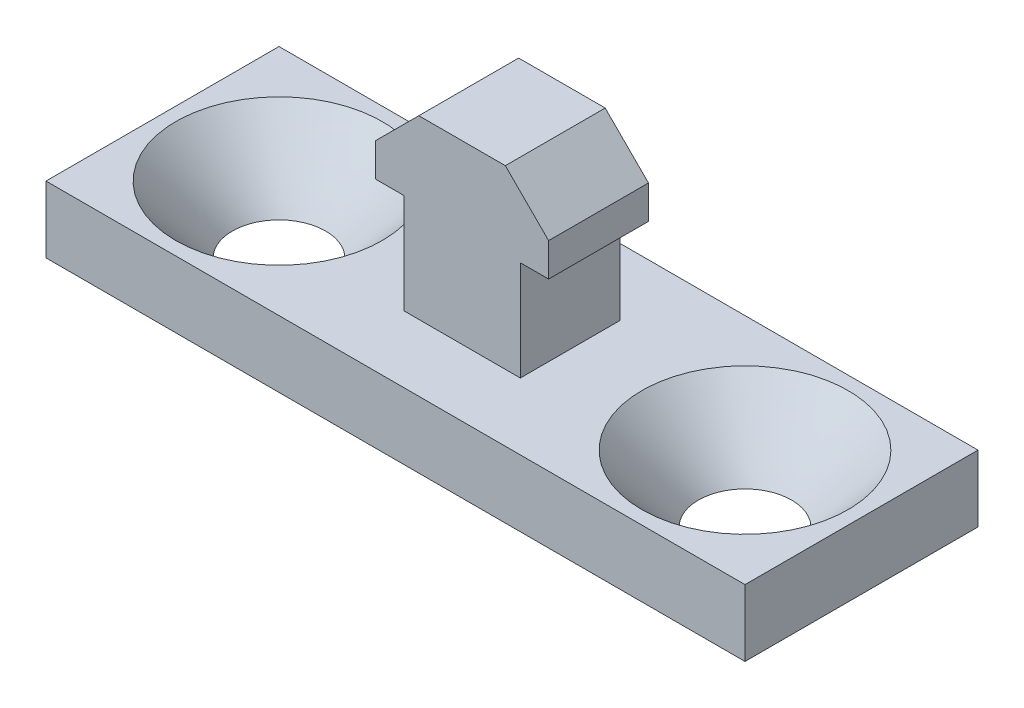
SolidWorks part; units mm, degrees
ref_plane "Front Plane" through (0, 0, 0) normal (0, 0, 1) x (1, 0, 0)
ref_plane "Top Plane" through (0, 0, 0) normal (0, 1, 0) x (1, 0, 0)
ref_plane "Right Plane" through (0, 0, 0) normal (1, 0, 0) x (0, 0, -1)
sketch "Sketch1" plane through (0, 0, 0) normal (0, 1, 0) x (1, 0, 0)
  line L1 (-10.5, -3.5) -> (10.5, -3.5)
  line L2 (-10.5, -3.5) -> (-10.5, 3.5)
  line L3 (-10.5, 3.5) -> (10.5, 3.5)
  line L4 (10.5, -3.5) -> (10.5, 3.5)
  line L5 (-10.5, -3.5) -> (10.5, 3.5) construction
  line L6 (-10.5, 3.5) -> (10.5, -3.5) construction
  point P0 (0, 0)
  dimension "D1" = 21
  dimension "D2" = 7
extrude "Boss-Extrude1" add sketch "Sketch1" along normal blind 2
sketch "Sketch2" plane through (0, 2, 0) normal (0, 1, 0) x (1, 0, 0)
  line L0 (-7, 0) -> (7, 0) construction
  circle A0 centre (-7, 0) radius 3.1
  circle A1 centre (7, 0) radius 3.1
  point P4 (0, 0)
  dimension "D2" = 6.2
  dimension "D1" = 14
sketch "Sketch3" plane through (0, 0, 0) normal (0, -1, 0) x (1, 0, 0)
  circle A0 centre (-7, 0) radius 1.4
  circle A1 centre (7, 0) radius 1.4
  dimension "D1" = 2.8
loft "Cut-Loft1" cut section "Sketch2" section "Sketch3" connector at (-8.8111, 2, 2.5159) connector at (-7.2216, 0, 1.3823)
mirror "Mirror1" about plane through (0, 0, 0) normal (1, 0, 0) of "Cut-Loft1"
sketch "Sketch4" plane through (0, 2, 0) normal (0, 1, 0) x (1, 0, 0)
  line L1 (-1.75, -1.5) -> (1.75, -1.5)
  line L2 (-1.75, -1.5) -> (-1.75, 1.5)
  line L3 (-1.75, 1.5) -> (1.75, 1.5)
  line L4 (1.75, -1.5) -> (1.75, 1.5)
  line L5 (-1.75, -1.5) -> (1.75, 1.5) construction
  line L6 (-1.75, 1.5) -> (1.75, -1.5) construction
  point P0 (0, 0)
  dimension "D1" = 3.5
  dimension "D2" = 3
extrude "Boss-Extrude2" add sketch "Sketch4" along normal blind 3
sketch "Sketch5" plane through (0, 0, 0) normal (0, 0, 1) x (1, 0, 0)
  line L0 (0, -994.9181) -> (0, 49005.0819) construction
  line L1 (-2.6, 5) -> (-2.6, 6)
  line L2 (-2.6, 5) -> (2.6, 5)
  line L3 (-2.6, 6) -> (-1.3, 7.3)
  line L4 (-1.3, 7.3) -> (1.3, 7.3)
  line L5 (2.6, 5) -> (2.6, 6)
  line L6 (2.6, 6) -> (1.3, 7.3)
  line L7 (0, -2.7501) -> (0, 2.7501) construction
  line L8 (-1.75, 5) -> (1.75, 5) construction
  point P1 (0, 0)
  point P5 (0, 5)
  point P8 (0, 7.3)
  point P11 (-0.5968, 5.4598)
  dimension "D1" = 1
  dimension "D2" = 2.3
  dimension "D3" = 5.2
  dimension "D4" = 2.6
extrude "Boss-Extrude3" add sketch "Sketch5" along normal up to surface and the other way up to surface up to face at (0, 3.5, 1.5) other way up to face at (0, 3.5, -1.5)
